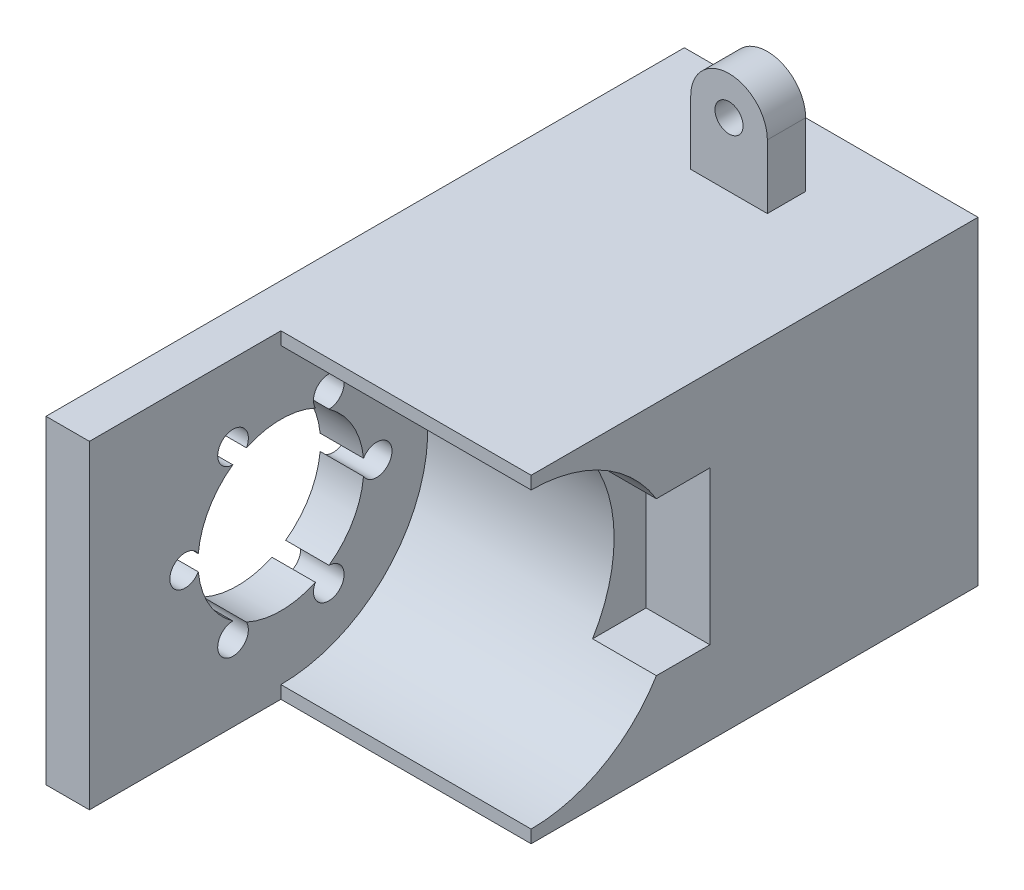
SolidWorks part; units mm, degrees
ref_plane "前视基准面" through (0, 0, 0) normal (0, 0, 1) x (1, 0, 0)
ref_plane "上视基准面" through (0, 0, 0) normal (0, 1, 0) x (1, 0, 0)
ref_plane "右视基准面" through (0, 0, 0) normal (1, 0, 0) x (0, 0, -1)
sketch "草图1" plane through (0, 0, 0) normal (0, 0, 1) x (1, 0, 0)
  line L9 (-11.5, 12.5) -> (11.5, 12.5)
  line L10 (-11.5, 12.5) -> (-11.5, -12.5)
  line L11 (-11.5, -12.5) -> (11.5, -12.5)
  line L12 (11.5, 12.5) -> (11.5, -12.5)
  line L13 (0, -12.5) -> (0, 12.5) construction
  line L14 (-11.5, 0) -> (11.5, 0) construction
  point P0 (0, 0)
  dimension "D1" = 23
  dimension "D2" = 25
extrude "凸台-拉伸1" add sketch "草图1" against normal blind 35 contours L12 L9 L10 L11 region at (0, 0, 0)
ref_axis "基准轴2" through (11.5, 0, 0) along (-1, 0, 0)
sketch "草图2" plane through (0, 0, 0) normal (0, 0, 1) x (1, 0, 0)
  line L0 (11.5, 0) -> (-11.5, 0) construction
  line L1 (11.5, 12.5) -> (11.5, -12.5) construction
  line L2 (11.5, 12.5) -> (11.5, -12.5) construction
  line L3 (11.5, 0) -> (11.5, -11.5)
  line L4 (11.5, -11.5) -> (-8.1, -11.5)
  line L9 (-8.1, -11.5) -> (-8.1, 0)
  line L10 (11.5, 0) -> (-8.1, 0)
  dimension "D1" = 11.5
  dimension "D2" = 19.6
revolve "切除-旋转2" cut sketch "草图2" angle 360 about axis through (11.5, 0, 0) along (-1, 0, 0)
ref_plane "基准面1" through (0, 0, 0) normal (0, 0, 1) x (1, 0, 0)
sketch "草图4" plane through (0, 0, 0) normal (0, 0, 1) x (1, 0, 0)
  line L0 (-8.1, 12.5) -> (-8.1, -12.5)
  line L1 (-11.5, 12.5) -> (11.5, 12.5) construction
  line L2 (-8.1, -12.5) -> (-11.5, -12.5)
  line L3 (-11.5, -12.5) -> (-11.5, 12.5)
  line L4 (-11.5, 12.5) -> (-8.1, 12.5)
  line L5 (-8.1, -11.5) -> (-8.1, 11.5) construction
  line L6 (-8.1, -11.5) -> (-8.1, 10.9) construction
  dimension "D1" = 25
extrude "凸台-拉伸2" add sketch "草图4" along normal blind 15
ref_plane "基准面2" through (-8.1, 0, 0) normal (1, 0, 0) x (0, 0, -1)
sketch "草图6" plane through (-8.1, 0, 0) normal (1, 0, 0) x (0, 0, -1)
  line L0 (0, 0) -> (7.5, 0) construction
  circle A0 centre (0, 0) radius 7.5 construction
  circle A1 centre (7.5, 0) radius 1.2
  circle A2 centre (3.75, -6.4952) radius 1.2
  circle A3 centre (-3.75, -6.4952) radius 1.2
  circle A5 centre (0, 0) radius 6.5
  circle A6 centre (-7.5, 0) radius 1.2
  circle A7 centre (-3.75, 6.4952) radius 1.2
  circle A8 centre (3.75, 6.4952) radius 1.2
  point P12 (0, 0)
  dimension "D1" = 15
  dimension "D2" = 2.4
  dimension "D5" = 13
  dimension "D3" = 6
extrude "切除-拉伸1" cut sketch "草图6" against normal blind 4 contours A7 | A6 | A8 | A1 | A3 | A2 | A5 region at (-8.1, 0, -7.5415) region at (-8.1, 6.5312, -3.7708) region at (-8.1, -6.5312, -3.7708) region at (-8.1, 6.5312, 3.7708) region at (-8.1, -6.5312, 3.7708) region at (-8.1, 0, 7.5415)
sketch "草图7" plane through (11.5, 0, 0) normal (1, 0, 0) x (0, 0, -1)
  line L1 (9, -6) -> (14, -6)
  line L2 (9, -6) -> (9, 6)
  line L3 (9, 6) -> (14, 6)
  line L4 (14, -6) -> (14, 6)
  line L5 (11.5, 6) -> (11.5, -6) construction
  line L6 (9, 0) -> (14, 0) construction
  arc A0 (0, -11.5) -> (0, 11.5) centre (0, 0) ccw construction
  point P4 (11.5, 0)
  dimension "D1" = 12
  dimension "D2" = 5
extrude "切除-拉伸3" cut sketch "草图7" against normal blind 5
sketch "草图8" plane through (0, 0, -35) normal (0, 0, -1) x (-1, 0, 0)
  line L0 (11.5, -12.5) -> (-11.5, -12.5) construction
  line L1 (0, -1026.5) -> (0, -20.5) construction
  line L2 (11.5, 0) -> (2.7493, 0) construction
  line L3 (3, 17.5) -> (3, 12.5)
  line L5 (-3, -17.5) -> (-3, -12.5)
  line L6 (-3, -12.5) -> (3, -12.5)
  line L7 (3, -17.5) -> (3, -12.5)
  line L8 (-3, 17.5) -> (-3, 12.5)
  line L9 (-3, -15) -> (3, -15) construction
  line L10 (0, -12.5) -> (0, 0) construction
  line L11 (-3, 12.5) -> (3, 12.5)
  line L19 (11.5, 0) -> (16.5, 0) construction
  arc A0 (-3, -17.5) -> (3, -17.5) centre (0, -17.5) ccw
  circle A1 centre (0, -17.5) radius 1.1
  arc A2 (-3, 17.5) -> (3, 17.5) centre (0, 17.5) cw
  circle A3 centre (0, 17.5) radius 1.1
  point P5 (0, -15)
  point P28 (0, -12.5)
  dimension "D3" = 3
  dimension "D4" = 2.2
  dimension "D1" = 5
  dimension "D2" = 6
extrude "凸台-拉伸3" add sketch "草图8" against normal blind 8
extrude "切除-拉伸4" cut sketch "草图8<2>" against normal blind 5
sketch "草图8<2>" plane through (0, 0, -35) normal (0, 0, -1) x (-1, 0, 0) same geometry as "草图8"
